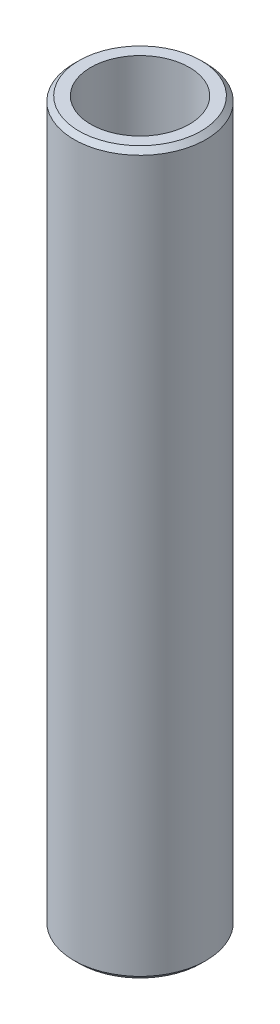
SolidWorks part; units mm, degrees
ref_plane "Front Plane" through (0, 0, 0) normal (0, 0, 1) x (1, 0, 0)
ref_plane "Top Plane" through (0, 0, 0) normal (0, 1, 0) x (1, 0, 0)
ref_plane "Right Plane" through (0, 0, 0) normal (1, 0, 0) x (0, 0, -1)
sketch "Sketch1" plane through (0, 0, 0) normal (0, 1, 0) x (1, 0, 0)
  circle A0 centre (0, 0) radius 45
  dimension "SHAFT_OD" = 90
extrude "Boss-Extrude1" add sketch "Sketch1" along normal blind 491.6955
sketch "Sketch2" plane through (0, 0, 0) normal (0, 1, 0) x (1, 0, 0)
  circle A0 centre (0, 0) radius 33.6465
  dimension "BORE_D" = 67.2929
extrude "Cut-Extrude1" cut sketch "Sketch2" along normal through all
chamfer "Chamfer1" distance 3.3317 angle 45 2 edges at (0, 491.6955, 45) (0, 0, 45)
